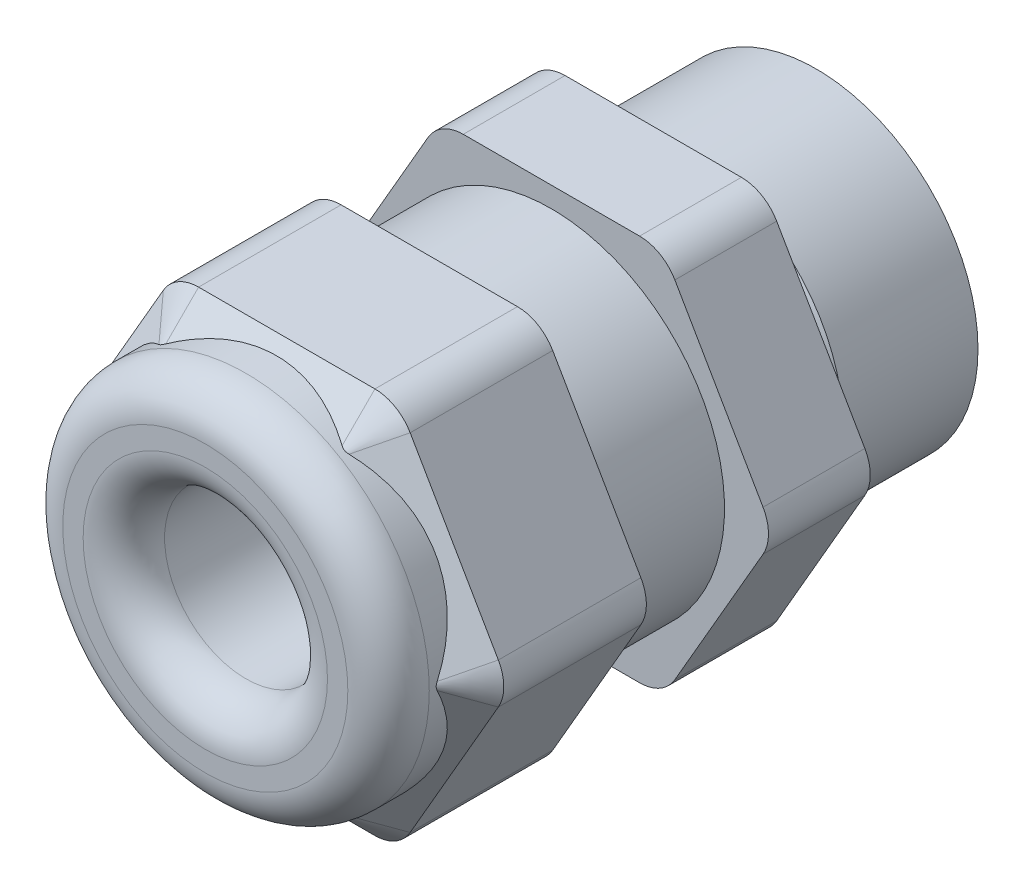
SolidWorks part; units mm, degrees
material "Nylon 6/10"
ref_plane "Front" through (0, 0, 0) normal (0, 0, 1) x (1, 0, 0)
ref_plane "Top" through (0, 0, 0) normal (0, 1, 0) x (1, 0, 0)
ref_plane "Right" through (0, 0, 0) normal (1, 0, 0) x (0, 0, -1)
sketch "Sketch1" plane through (0, 0, 0) normal (0, 0, 1) x (1, 0, 0)
  line L1 (10.9697, 0) -> (5.4848, 9.5)
  line L2 (5.4848, 9.5) -> (-5.4848, 9.5)
  line L3 (-5.4848, 9.5) -> (-10.9697, 0)
  line L4 (-10.9697, 0) -> (-5.4848, -9.5)
  line L5 (-5.4848, -9.5) -> (5.4848, -9.5)
  line L6 (5.4848, -9.5) -> (10.9697, 0)
  circle A0 centre (0, 0) radius 9.5 construction
  dimension "D1" = 19
extrude "Boss-Extrude1" add sketch "Sketch1" along normal blind 22
sketch "Sketch2" plane through (0, 0, 0) normal (0, 0, -1) x (-1, 0, 0)
  circle A0 centre (0, 0) radius 7.95
  dimension "D1" = 15.9
extrude "Boss-Extrude2" add sketch "Sketch2" along normal blind 8
sketch "Sketch3" plane through (0, 0, 22) normal (0, 0, 1) x (1, 0, 0)
  circle A0 centre (0, 0) radius 9
  dimension "D1" = 18
extrude "Cut-Extrude1" cut sketch "Sketch3" against normal blind 2 flip side to cut
fillet "Fillet1" radius 2 6 edges at (5.4848, -9.5, 10) (-5.4848, -9.5, 10) (-10.9697, 0, 10) (-5.4848, 9.5, 10) (10.9697, 0, 10) (5.4848, 9.5, 10)
chamfer "Chamfer1" distance 2 angle 45 12 edges at (0, -9.5, 20) (5.3301, -9.2321, 20) (-5.3301, -9.2321, 20) (8.2272, -4.75, 20) (-8.2272, -4.75, 20) (10.6603, 0, 20) (-10.6603, 0, 20) (8.2272, 4.75, 20) (-8.2272, 4.75, 20) (5.3301, 9.2321, 20) (-5.3301, 9.2321, 20) (0, 9.5, 20)
fillet "Fillet2" radius 2 1 edges at (9, 0, 22)
sketch "Sketch4" plane through (0, 0, 0) normal (0, 0, -1) x (-1, 0, 0)
  circle A0 centre (0, 0) radius 8.5
  dimension "D1" = 17
extrude "Cut-Extrude2" cut sketch "Sketch4" against normal blind 6 from offset 5 flip side to cut offset against normal yes
sketch "Sketch5" plane through (0, 0, 22) normal (0, 0, 1) x (1, 0, 0)
  circle A0 centre (0, 0) radius 4
  dimension "D1" = 8
extrude "Cut-Extrude3" cut sketch "Sketch5" against normal blind 3
fillet "Fillet3" radius 2 1 edges at (4, 0, 22)
sketch "Sketch6" plane through (0, 0, -8) normal (0, 0, -1) x (-1, 0, 0)
  circle A0 centre (0, 0) radius 5
  dimension "D1" = 10
extrude "Cut-Extrude4" cut sketch "Sketch6" against normal up to surface (19 mm away) up to face at (0, 0, 11)
sketch "Sketch7" plane through (0, 0, 19) normal (0, 0, 1) x (1, 0, 0)
  line L0 (-2.5, 0) -> (0, 0) construction
  circle A0 centre (-2.5, 0) radius 0.7
  circle A1 centre (-1.25, 2.1651) radius 0.7
  circle A2 centre (1.25, 2.1651) radius 0.7
  circle A3 centre (2.5, 0) radius 0.7
  circle A4 centre (1.25, -2.1651) radius 0.7
  circle A5 centre (-1.25, -2.1651) radius 0.7
  point P17 (0, 0)
  dimension "D1" = 1.4
  dimension "D2" = 2.5
  dimension "D3" = 6
extrude "Cut-Extrude5" cut sketch "Sketch7" against normal through all
sketch "Sketch8" plane through (0, 0, 0) normal (0, 1, 0) x (1, 0, 0)
  line L1 (-6.0622, 0) -> (-10.3923, 0) construction
  line L2 (0, 0) -> (0, 50000) construction
  line L3 (-6, 0.125) -> (0, 0.125) construction
  line L4 (-6.75, 0.875) -> (-7.95, 0.875)
  line L5 (-7.95, 8) -> (-7.95, 0) construction
  line L6 (-7.95, 0.875) -> (-7.95, -0.625)
  line L7 (-7.95, -0.625) -> (-6.75, -0.625)
  arc A0 (-6.75, -0.625) -> (-6.75, 0.875) centre (-6.75, 0.125) ccw
  dimension "D1" = 1.5
  dimension "D3" = 6
  dimension "D2" = 0.125
revolve "Cut-Revolve1" cut sketch "Sketch8" angle 360 about L2
chamfer "Chamfer2" distance 0.5 angle 30 2 edges at (7.95, 0, 0) (7.95, 0, -0.875) first distance on face at (7.95, 0, 0) first distance on face at (-7.95, 0, -8)
sketch "Sketch9" plane through (0, 0, 19) normal (0, 0, 1) x (1, 0, 0)
  circle A1 centre (0, 0) radius 4
  circle A2 centre (0, 0) radius 4
  dimension "D1" = 0
extrude "Cut-Extrude6" cut sketch "Sketch9" against normal through all
